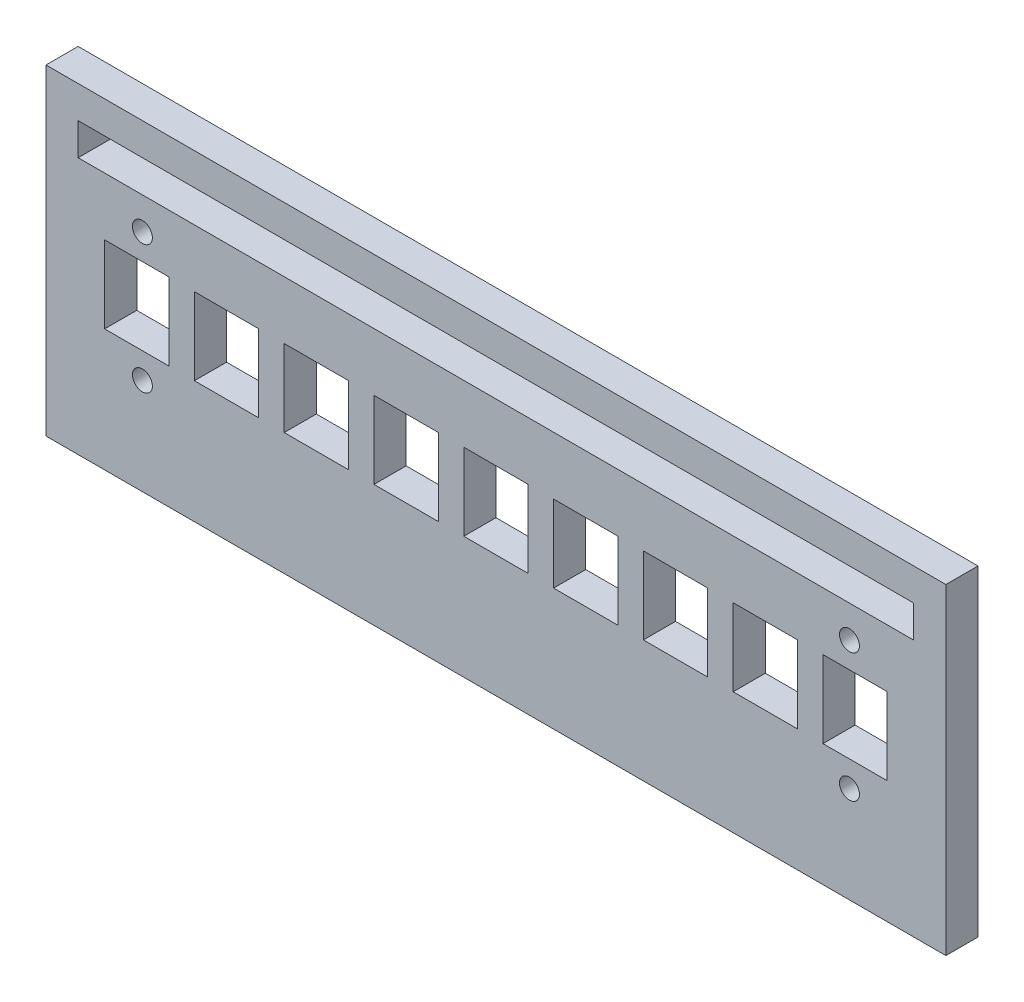
SolidWorks part; units mm, degrees
ref_plane "Plan de face" through (0, 0, 0) normal (0, 0, 1) x (1, 0, 0)
ref_plane "Plan de dessus" through (0, 0, 0) normal (0, 1, 0) x (1, 0, 0)
ref_plane "Plan de droite" through (0, 0, 0) normal (1, 0, 0) x (0, 0, -1)
sketch "Esquisse1" plane through (0, 0, 0) normal (0, 0, 1) x (1, 0, 0)
  line L0 (8.97, -6) -> (8.97, 6)
  line L5 (-70, -25) -> (70, -25)
  line L6 (-70, -25) -> (-70, 25)
  line L7 (-70, 25) -> (70, 25)
  line L8 (70, -25) -> (70, 25)
  line L9 (-70, -25) -> (70, 25) construction
  line L10 (-70, 25) -> (70, -25) construction
  line L11 (-5, -6) -> (5, -6)
  line L12 (-5, -6) -> (-5, 6)
  line L13 (-5, 6) -> (5, 6)
  line L14 (5, -6) -> (5, 6)
  line L15 (-5, -6) -> (5, 6) construction
  line L16 (-5, 6) -> (5, -6) construction
  line L17 (8.97, -6) -> (18.97, -6)
  line L18 (18.97, -6) -> (18.97, 6)
  line L19 (8.97, 6) -> (18.97, 6)
  line L20 (22.94, -6) -> (22.94, 6)
  line L21 (22.94, -6) -> (32.94, -6)
  line L22 (32.94, -6) -> (32.94, 6)
  line L23 (22.94, 6) -> (32.94, 6)
  line L24 (36.91, -6) -> (36.91, 6)
  line L25 (36.91, -6) -> (46.91, -6)
  line L26 (46.91, -6) -> (46.91, 6)
  line L27 (36.91, 6) -> (46.91, 6)
  line L28 (50.88, -6) -> (50.88, 6)
  line L29 (50.88, -6) -> (60.88, -6)
  line L30 (60.88, -6) -> (60.88, 6)
  line L31 (50.88, 6) -> (60.88, 6)
  line L32 (-5, -6) -> (8.97, -6) construction
  line L33 (-18.97, -6) -> (-18.97, 6)
  line L34 (-18.97, -6) -> (-8.97, -6)
  line L35 (-8.97, -6) -> (-8.97, 6)
  line L36 (-18.97, 6) -> (-8.97, 6)
  line L37 (-32.94, -6) -> (-32.94, 6)
  line L38 (-32.94, -6) -> (-22.94, -6)
  line L39 (-22.94, -6) -> (-22.94, 6)
  line L40 (-32.94, 6) -> (-22.94, 6)
  line L41 (-46.91, -6) -> (-46.91, 6)
  line L42 (-46.91, -6) -> (-36.91, -6)
  line L43 (-36.91, -6) -> (-36.91, 6)
  line L44 (-46.91, 6) -> (-36.91, 6)
  line L45 (-60.88, -6) -> (-60.88, 6)
  line L46 (-60.88, -6) -> (-50.88, -6)
  line L47 (-50.88, -6) -> (-50.88, 6)
  line L48 (-60.88, 6) -> (-50.88, 6)
  line L49 (-5, -6) -> (-18.97, -6) construction
  line L50 (0, 0) -> (0, 7.7631) construction
  line L51 (0, 0) -> (6.8675, 0) construction
  line L54 (-65, 20) -> (65, 20)
  line L55 (-65, 20) -> (-65, 15)
  line L56 (-65, 15) -> (65, 15)
  line L57 (65, 20) -> (65, 15)
  circle A0 centre (-55, -10) radius 1.55
  circle A1 centre (-55, 10) radius 1.55
  circle A2 centre (55, -10) radius 1.55
  circle A3 centre (55, 10) radius 1.55
  point P0 (0, 0)
  point P7 (0, 0)
  point P60 (0, 0)
  point P61 (0, 0)
  point P62 (0, 0)
  dimension "D9" = 3.1
  dimension "D1" = 140
  dimension "D2" = 50
  dimension "D3" = 10
  dimension "D4" = 12
  dimension "D6" = 13.97
  dimension "D8" = 13.97
  dimension "D10" = 15
  dimension "D11" = 15
  dimension "D12" = 0
  dimension "D13" = 5
  dimension "D14" = 5
  dimension "D15" = 5
  dimension "D16" = 5
  dimension "D5" = 5
  dimension "D7" = 5
extrude "Boss.-Extru.1" add sketch "Esquisse1" against normal blind 5
